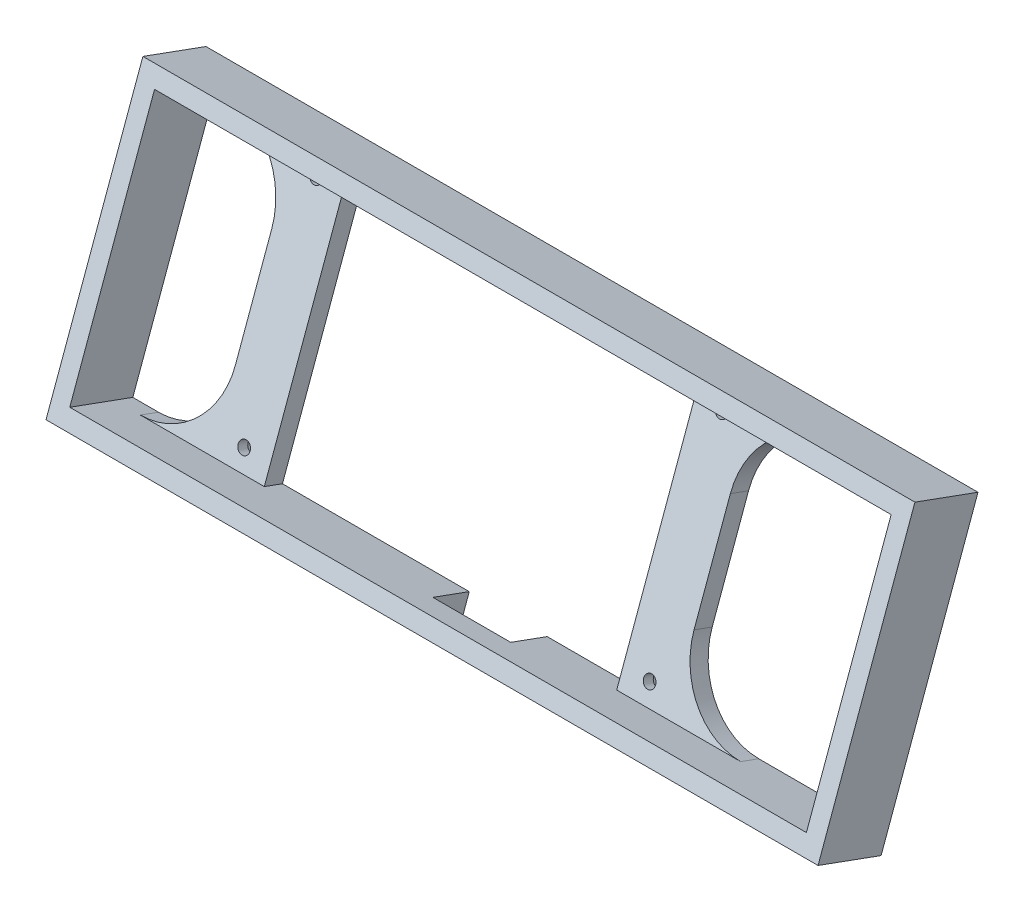
SolidWorks part; units mm, degrees
ref_plane "Plan de face" through (0, 0, 0) normal (0, 0, 1) x (1, 0, 0)
ref_plane "Plan de dessus" through (0, 0, 0) normal (0, 1, 0) x (1, 0, 0)
ref_plane "Plan de droite" through (0, 0, 0) normal (1, 0, 0) x (0, 0, -1)
ref_axis "Axe1" through (-88.99, 0, 0) along (1, 0, 0)
ref_plane "Plan1" through (0, 0, 0) normal (0, 0.342, 0.9397) x (1, 0, 0)
sketch "Esquisse1" plane through (0, 0, 0) normal (0, 0.342, 0.9397) x (1, 0, 0)
  line L1 (-104, -35) -> (104, -35)
  line L2 (-104, -35) -> (-104, 35)
  line L3 (-104, 35) -> (104, 35)
  line L4 (104, -35) -> (104, 35)
  line L5 (-104, -35) -> (104, 35) construction
  line L6 (-104, 35) -> (104, -35) construction
  line L7 (-109, 40) -> (109, 40)
  line L8 (-109, 40) -> (-109, -40)
  line L9 (-109, -40) -> (109, -40)
  line L10 (109, 40) -> (109, -40)
  line L11 (-109, 40) -> (109, -40) construction
  line L12 (-109, -40) -> (109, 40) construction
  point P0 (0, 0)
  point P5 (0, 0)
  dimension "D1" = 208
  dimension "D2" = 70
  dimension "D3" = 5
  dimension "D4" = 5
extrude "Boss.-Extru.1" add sketch "Esquisse1" along normal blind 16.5
sketch "Esquisse2" plane through (0, 0, 0) normal (0, -0.342, -0.9397) x (-1, 0, 0)
  line L0 (104, 0) -> (69.25, 0) construction
  line L1 (-45.25, 29.75) -> (69.25, 29.75) construction
  line L2 (-45.25, 29.75) -> (-45.25, -29.75) construction
  line L3 (-45.25, -29.75) -> (69.25, -29.75) construction
  line L4 (69.25, 29.75) -> (69.25, -29.75) construction
  line L5 (104, 35) -> (104, -35) construction
  line L6 (109, -40) -> (-109, -40) construction
  line L7 (-52.75, 40) -> (-37.75, 40)
  line L8 (-52.75, 40) -> (-52.75, -40)
  line L9 (-52.75, -40) -> (-37.75, -40)
  line L10 (-37.75, 40) -> (-37.75, -40)
  line L11 (-52.75, 40) -> (-37.75, -40) construction
  line L12 (-52.75, -40) -> (-37.75, 40) construction
  line L14 (61.75, 40) -> (76.75, 40)
  line L15 (61.75, 40) -> (61.75, -40)
  line L16 (61.75, -40) -> (76.75, -40)
  line L17 (76.75, 40) -> (76.75, -40)
  line L18 (61.75, 40) -> (76.75, -40) construction
  line L19 (61.75, -40) -> (76.75, 40) construction
  circle A0 centre (69.25, 29.75) radius 3.25
  circle A1 centre (69.25, -29.75) radius 3.25
  circle A2 centre (-45.25, 29.75) radius 3.25
  circle A3 centre (-45.25, -29.75) radius 3.25
  point P8 (-45.25, 0)
  dimension "D1" = 6.5
  dimension "D2" = 59.5
  dimension "D3" = 34.75
  dimension "D4" = 114.5
  dimension "D5" = 15
extrude "Boss.-Extru.2" add sketch "Esquisse2" along normal blind 2.45
sketch "Esquisse3" plane through (0, 5.6433, 15.5049) normal (0, 0.342, 0.9397) x (1, 0, 0)
  line L0 (-104, -35) -> (104, -35) construction
  line L1 (-9, -35) -> (13, -35)
  line L2 (-9, -35) -> (-9, -40)
  line L3 (-9, -40) -> (13, -40)
  line L4 (13, -35) -> (13, -40)
  line L5 (-109, -40) -> (109, -40) construction
  line L6 (-104, 35) -> (-104, -35) construction
  dimension "D1" = 95
  dimension "D2" = 22
extrude "Enlèv. mat.-Extru.1" cut sketch "Esquisse3" against normal up to surface (16.5 mm away) up to face at (-12, -35.2385, 12.8258)
sketch "Esquisse4" plane through (0, 0, 0) normal (0, 0.342, 0.9397) x (1, 0, 0)
  line L0 (52.75, 35) -> (37.75, 35) construction
  line L1 (37.75, 35) -> (37.75, -35) construction
  line L2 (37.75, -35) -> (52.75, -35) construction
  line L3 (52.75, -35) -> (52.75, 35) construction
  line L4 (-61.75, 35) -> (-76.75, 35) construction
  line L5 (-76.75, 35) -> (-76.75, -35) construction
  line L6 (-76.75, -35) -> (-61.75, -35) construction
  line L7 (-61.75, -35) -> (-61.75, 35) construction
  line L8 (52.75, 35) -> (37.75, 35)
  line L9 (37.75, 35) -> (37.75, -35)
  line L10 (37.75, -35) -> (52.75, -35)
  line L11 (52.75, -35) -> (52.75, 35)
  line L12 (-61.75, 35) -> (-76.75, 35)
  line L13 (-76.75, 35) -> (-76.75, -35)
  line L14 (-76.75, -35) -> (-61.75, -35)
  line L15 (-61.75, -35) -> (-61.75, 35)
  circle A0 centre (-69.25, 29.75) radius 1.7
  circle A1 centre (-69.25, -29.75) radius 1.7
  circle A2 centre (45.25, -29.75) radius 1.7
  circle A3 centre (45.25, 29.75) radius 1.7
  dimension "D1" = 3.4
extrude "Boss.-Extru.3" add sketch "Esquisse4" along normal blind 3
fillet "Congé1" radius 20 4 edges at (52.75, -32.3762, 13.3802) (52.75, 33.4023, -10.5612) (-76.75, -32.3762, 13.3802) (-76.75, 33.4023, -10.5612)
sketch "Esquisse7" plane through (0, 5.6433, 15.5049) normal (0, 0.342, 0.9397) x (1, 0, 0)
  line L1 (-9, -35) -> (13, -35)
  line L2 (-9, -35) -> (-9, -40)
  line L3 (-9, -40) -> (13, -40)
  line L4 (13, -35) -> (13, -40)
extrude "Boss.-Extru.5" add sketch "Esquisse7" against normal blind 8
sketch "Esquisse8" plane through (0, 0, 0) normal (0, -0.342, -0.9397) x (-1, 0, 0)
  line L0 (76.75, -15) -> (76.75, -40) construction
  line L1 (76.75, -40) -> (109, -40) construction
  line L2 (109, -40) -> (109, 40) construction
  line L3 (109, 40) -> (76.75, 40) construction
  line L4 (76.75, 40) -> (76.75, 15) construction
  line L5 (96.75, 35) -> (104, 35) construction
  line L6 (104, 35) -> (104, -35) construction
  line L7 (104, -35) -> (96.75, -35) construction
  line L8 (-52.75, 15) -> (-52.75, 40) construction
  line L9 (-52.75, 40) -> (-109, 40) construction
  line L10 (-109, 40) -> (-109, -40) construction
  line L11 (-109, -40) -> (-52.75, -40) construction
  line L12 (-52.75, -40) -> (-52.75, -15) construction
  line L13 (-72.75, -35) -> (-104, -35) construction
  line L14 (-104, -35) -> (-104, 35) construction
  line L15 (-104, 35) -> (-72.75, 35) construction
  line L16 (76.75, -15) -> (76.75, -40)
  line L17 (76.75, -40) -> (109, -40)
  line L18 (109, -40) -> (109, 40)
  line L19 (109, 40) -> (76.75, 40)
  line L20 (76.75, 40) -> (76.75, 15)
  line L21 (96.75, 35) -> (104, 35)
  line L22 (104, 35) -> (104, -35)
  line L23 (104, -35) -> (96.75, -35)
  line L24 (-52.75, 15) -> (-52.75, 40)
  line L25 (-52.75, 40) -> (-109, 40)
  line L26 (-109, 40) -> (-109, -40)
  line L27 (-109, -40) -> (-52.75, -40)
  line L28 (-52.75, -40) -> (-52.75, -15)
  line L29 (-72.75, -35) -> (-104, -35)
  line L30 (-104, -35) -> (-104, 35)
  line L31 (-104, 35) -> (-72.75, 35)
  line L32 (61.75, -35) -> (9, -35) construction
  line L33 (9, -35) -> (9, -40) construction
  line L34 (9, -40) -> (61.75, -40) construction
  line L35 (61.75, -40) -> (61.75, -35) construction
  line L36 (-37.75, -40) -> (-13, -40) construction
  line L37 (-13, -40) -> (-13, -35) construction
  line L38 (-13, -35) -> (-37.75, -35) construction
  line L39 (-37.75, -35) -> (-37.75, -40) construction
  line L40 (-37.75, 40) -> (-37.75, 35) construction
  line L41 (-37.75, 35) -> (61.75, 35) construction
  line L42 (61.75, 35) -> (61.75, 40) construction
  line L43 (61.75, 40) -> (-37.75, 40) construction
  line L44 (61.75, -35) -> (9, -35)
  line L45 (9, -35) -> (9, -40)
  line L46 (9, -40) -> (61.75, -40)
  line L47 (61.75, -40) -> (61.75, -35)
  line L48 (-37.75, -40) -> (-13, -40)
  line L49 (-13, -40) -> (-13, -35)
  line L50 (-13, -35) -> (-37.75, -35)
  line L51 (-37.75, -35) -> (-37.75, -40)
  line L52 (-37.75, 40) -> (-37.75, 35)
  line L53 (-37.75, 35) -> (61.75, 35)
  line L54 (61.75, 35) -> (61.75, 40)
  line L55 (61.75, 40) -> (-37.75, 40)
  arc A0 (96.75, 35) -> (76.75, 15) centre (96.75, 15) ccw construction
  arc A1 (76.75, -15) -> (96.75, -35) centre (96.75, -15) ccw construction
  arc A2 (-72.75, -35) -> (-52.75, -15) centre (-72.75, -15) ccw construction
  arc A3 (-52.75, 15) -> (-72.75, 35) centre (-72.75, 15) ccw construction
  arc A4 (96.75, 35) -> (76.75, 15) centre (96.75, 15) ccw
  arc A5 (76.75, -15) -> (96.75, -35) centre (96.75, -15) ccw
  arc A6 (-72.75, -35) -> (-52.75, -15) centre (-72.75, -15) ccw
  arc A7 (-52.75, 15) -> (-72.75, 35) centre (-72.75, 15) ccw
extrude "Boss.-Extru.6" add sketch "Esquisse8" along normal up to surface (2.45 mm away) up to face at (45.25, 30.1719, -13.5889)
ref_plane "Plan2" through (0, 43.231, 0) normal (0, 1, 0) x (1, 0, 0)
sketch "Esquisse9" plane through (0, 43.231, 0) normal (0, 1, 0) x (1, 0, 0)
  line L0 (-127, 0.1759) -> (127, 0.1759) construction
  line L1 (-109, -1.8241) -> (-109, -29.1857) construction
  line L2 (0, -1.8241) -> (0, 0.1759) construction
  line L3 (109, -1.8241) -> (-109, -1.8241) construction
  line L4 (-142, 26.662) -> (142, 26.662)
  line L5 (0, 26.662) -> (0, 0.1759) construction
  circle A0 centre (127, 0.1759) radius 11.1
  circle A1 centre (-127, 0.1759) radius 11.1
  dimension "D1" = 22.2
  dimension "D2" = 18
  dimension "D3" = 2
  dimension "D4" = 284
